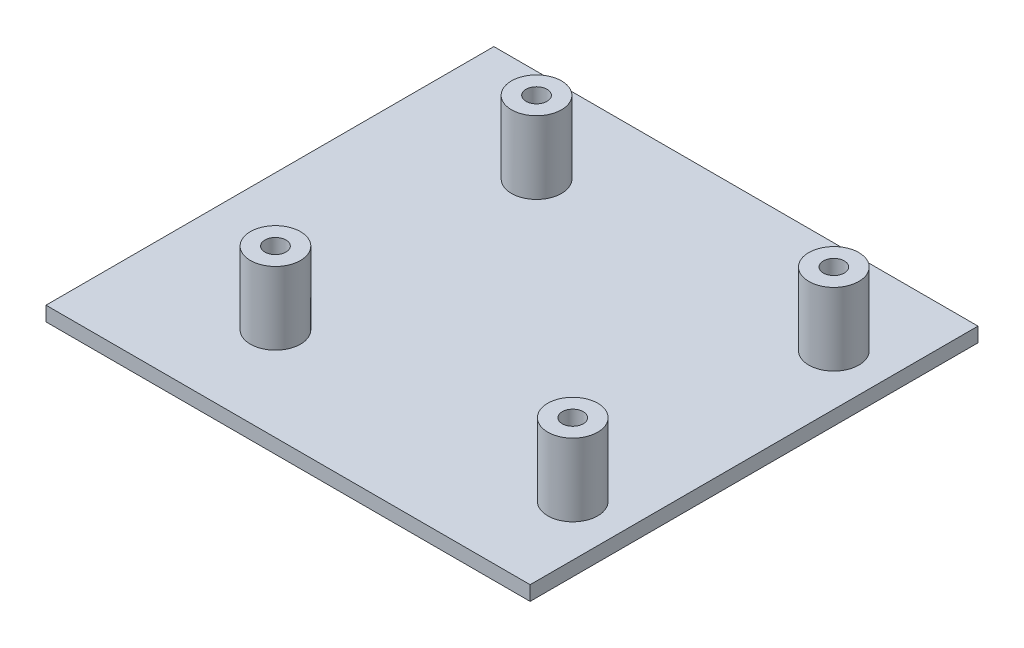
SolidWorks part; units mm, degrees
ref_plane "Front Plane" through (0, 0, 0) normal (0, 0, 1) x (1, 0, 0)
ref_plane "Top Plane" through (0, 0, 0) normal (0, 1, 0) x (1, 0, 0)
ref_plane "Right Plane" through (0, 0, 0) normal (1, 0, 0) x (0, 0, -1)
sketch "Sketch1" plane through (0, 0, 0) normal (0, 1, 0) x (1, 0, 0)
  line L1 (0, 0) -> (66.76, 0)
  line L2 (0, 0) -> (0, 61.76)
  line L3 (0, 61.76) -> (66.76, 61.76)
  line L4 (66.76, 0) -> (66.76, 61.76)
  dimension "D1" = 66.76
  dimension "D2" = 61.76
extrude "Boss-Extrude3" add sketch "Sketch1" against normal blind 2
sketch "Sketch2" plane through (0, 0, 0) normal (0, 1, 0) x (1, 0, 0)
  line L0 (63.76, 8.88) -> (14.76, 8.88) construction
  line L1 (0, 61.76) -> (0, 0) construction
  line L2 (18.76, 12.88) -> (59.76, 12.88) construction
  line L3 (0, 0) -> (66.76, 0) construction
  line L4 (66.76, 0) -> (66.76, 61.76) construction
  line L5 (66.76, 61.76) -> (0, 61.76) construction
  line L6 (63.76, 59.75) -> (63.76, 2.01) construction
  line L7 (2.01, 2.01) -> (64.75, 2.01) construction
  line L8 (2.01, 2.01) -> (2.01, 59.75) construction
  line L9 (2.01, 59.75) -> (64.75, 59.75) construction
  line L10 (64.75, 2.01) -> (64.75, 59.75) construction
  line L11 (18.76, 12.88) -> (18.76, 48.88) construction
  line L12 (18.76, 48.88) -> (59.76, 48.88) construction
  line L13 (59.76, 12.88) -> (59.76, 48.88) construction
  line L14 (14.76, 8.88) -> (14.76, 52.88) construction
  line L15 (14.76, 52.88) -> (63.76, 52.88) construction
  line L16 (0, 30.88) -> (66.76, 30.88) construction
  line L17 (39.26, 12.88) -> (39.26, 48.88) construction
  circle A0 centre (59.76, 12.88) radius 1.45
  circle A4 centre (59.76, 12.88) radius 3.45
  circle A5 centre (18.76, 12.88) radius 3.45
  circle A6 centre (18.76, 12.88) radius 1.45
  circle A7 centre (18.76, 48.88) radius 1.45
  circle A8 centre (59.76, 48.88) radius 1.45
  circle A9 centre (59.76, 48.88) radius 3.45
  circle A10 centre (18.76, 48.88) radius 3.45
  dimension "D13" = 2.9
  dimension "D11" = 6.9
  dimension "D1" = 2.01
  dimension "D2" = 2.01
  dimension "D3" = 0.99
  dimension "D4" = 2.01
  dimension "D5" = 2.01
  dimension "D6" = 49
  dimension "D7" = 44
  dimension "D8" = 22
  dimension "D9" = 4
  dimension "D10" = 4
  dimension "D12" = 4
extrude "Boss-Extrude4" add sketch "Sketch2" along normal blind 10
sketch "Sketch3" plane through (0, 0, 0) normal (0, 1, 0) x (1, 0, 0)
  line L0 (0, 61.76) -> (0, 0) construction
  line L3 (2.01, 59.75) -> (64.75, 59.75) construction
  line L6 (2.01, 59.75) -> (2.01, 2.01) construction
  line L11 (2.01, 2.01) -> (64.75, 2.01) construction
  line L12 (64.75, 59.75) -> (64.75, 2.01) construction
  line L13 (0, 0) -> (66.76, 0) construction
  line L14 (66.76, 61.76) -> (0, 61.76) construction
  line L15 (66.76, 0) -> (66.76, 61.76) construction
  dimension "D1" = 2.01
  dimension "D2" = 2.01
  dimension "D3" = 2.01
  dimension "D4" = 2.01
